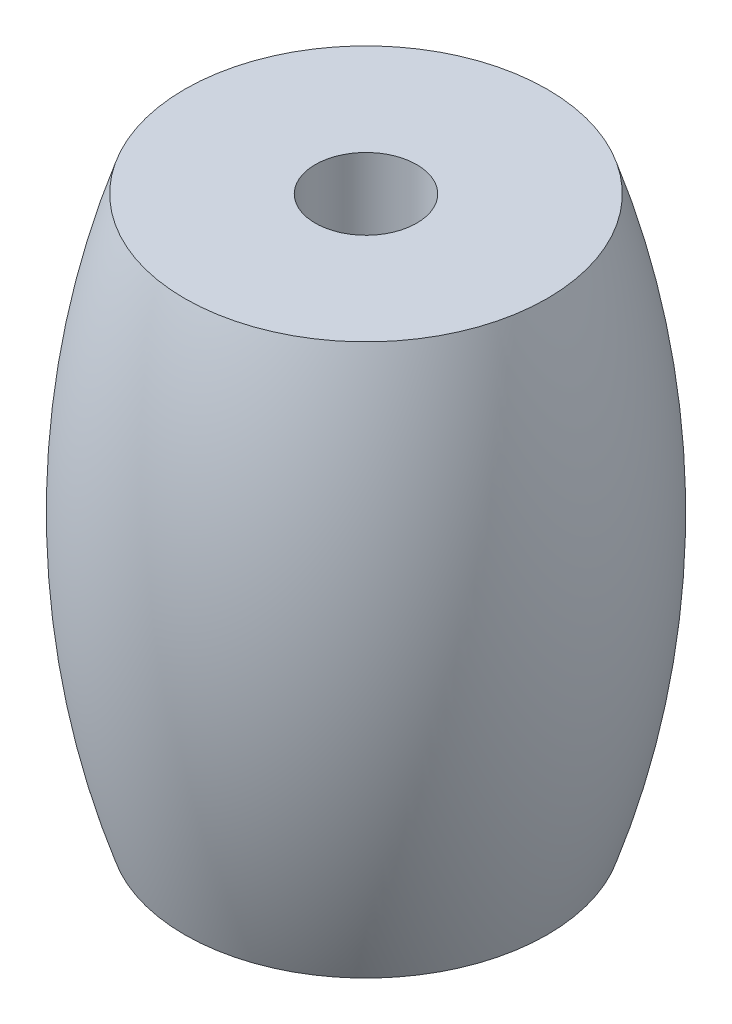
SolidWorks part; units mm, degrees
ref_plane "前视基准面" through (0, 0, 0) normal (0, 0, 1) x (1, 0, 0)
ref_plane "上视基准面" through (0, 0, 0) normal (0, 1, 0) x (1, 0, 0)
ref_plane "右视基准面" through (0, 0, 0) normal (1, 0, 0) x (0, 0, -1)
sketch "草图1" plane through (0, 0, 0) normal (0, 0, 1) x (1, 0, 0)
  line L0 (-1.75, 16.5644) -> (-1.75, -2.4356)
  line L1 (-1.75, -2.4356) -> (-6.25, -2.4356)
  line L2 (-1.75, 16.5644) -> (-6.25, 16.5644)
  line L3 (0, 0) -> (0, 19.2124) construction
  arc A1 (-6.25, 16.5644) -> (-6.25, -2.4356) centre (22.2061, 7.0644) ccw
  dimension "D1" = 1.75
  dimension "D2" = 19
  dimension "D3" = 4.5
  dimension "D4" = 4.5
revolve "旋转1" add sketch "草图1" angle 360 about L3
